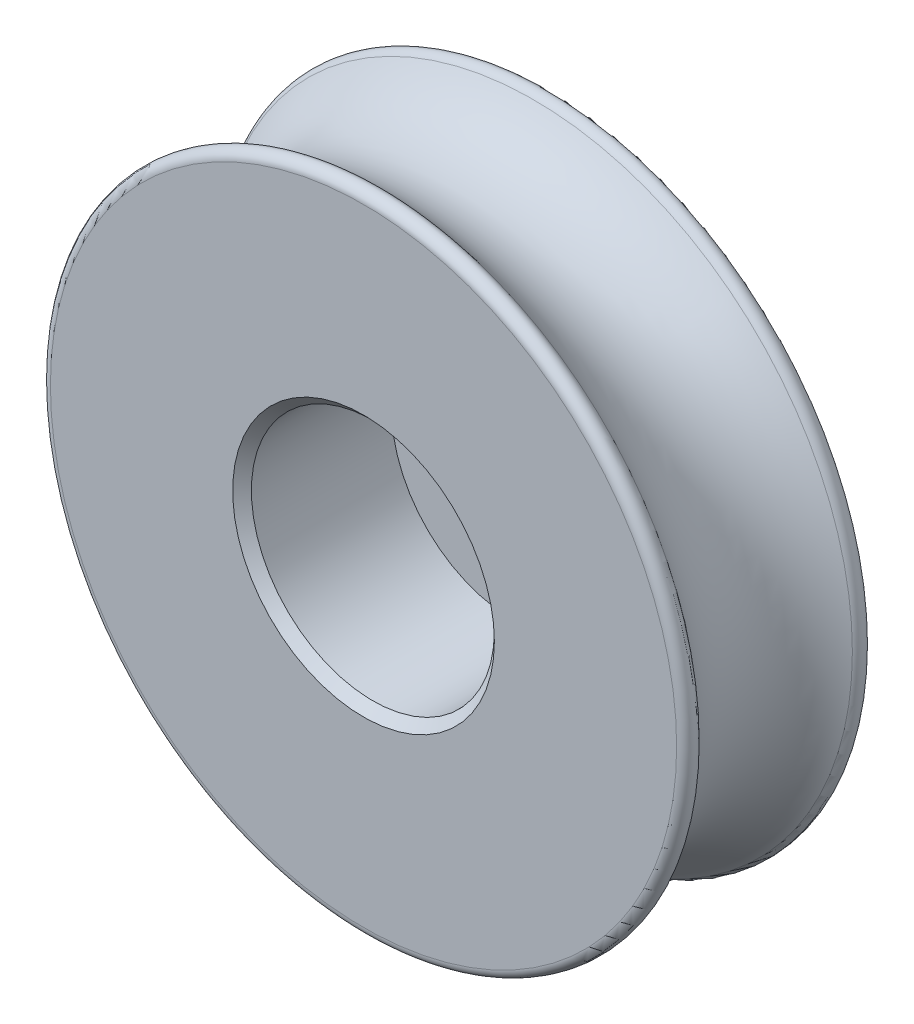
SolidWorks part; units mm, degrees
ref_plane "Front Plane" through (0, 0, 0) normal (0, 0, 1) x (1, 0, 0)
ref_plane "Top Plane" through (0, 0, 0) normal (0, 1, 0) x (1, 0, 0)
ref_plane "Right Plane" through (0, 0, 0) normal (1, 0, 0) x (0, 0, -1)
ref_axis "X Axis" through (-88.99, 0, 0) along (1, 0, 0)
ref_axis "Y Axis" through (0, 55, 0) along (0, -1, 0)
ref_axis "Z Axis" through (0, 0, -88.99) along (0, 0, 1)
sketch "Sketch2" plane through (0, 0, 0) normal (0, 1, 0) x (1, 0, 0)
  line L1 (1.1, 4) -> (7.6, 4)
  line L2 (7.6, 0) -> (2.6, 0)
  line L3 (2.6, 3.2) -> (2.6, 0)
  line L4 (0, 0) -> (0, 4) construction
  line L5 (2.6, 3.2) -> (1.1, 3.2)
  line L6 (1.1, 3.2) -> (1.1, 4)
  arc A0 (7.6, 4) -> (7.6, 0) centre (8.05, 2) ccw
  point P2 (1.0066, 4)
  point P6 (0, 0)
  dimension "D2" = 12
  dimension "D4" = 5
  dimension "D1" = 5.2
  dimension "D3" = 4
  dimension "D5" = 2.2
  dimension "D6" = 3.2
  dimension "D7" = 15.2
revolve "Revolve1" add sketch "Sketch2" angle 360 about L4
fillet "Fillet1" radius 0.2 2 edges at (7.6, 0, -4) (7.6, 0, 0)
chamfer "Chamfer2" distance 0.2 angle 45 2 edges at (1.1, 0, -4) (2.6, 0, 0)
